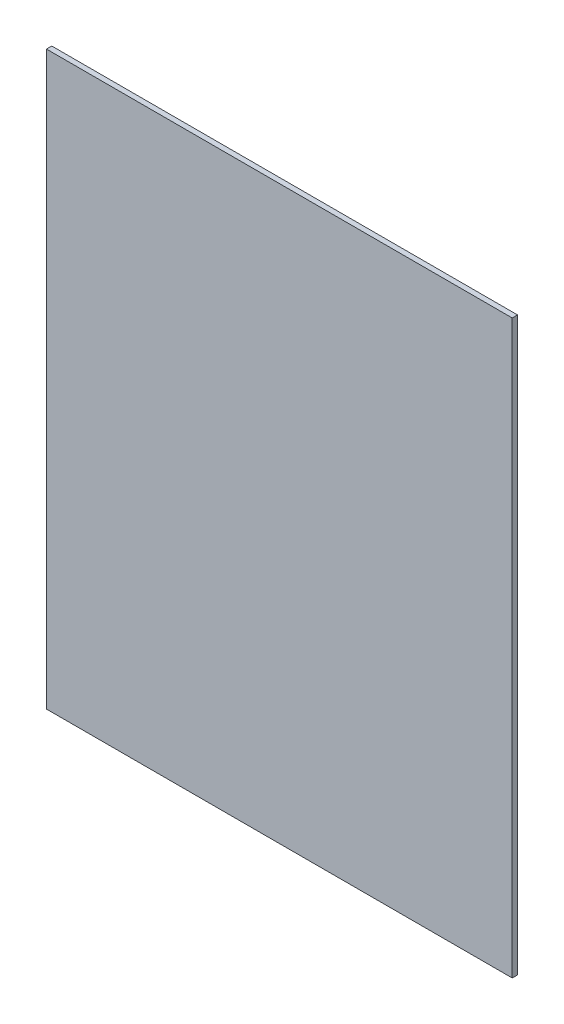
SolidWorks part; units mm, degrees
material "6061-T6 (SS)"
ref_plane "Front Plane" through (0, 0, 0) normal (0, 0, 1) x (1, 0, 0)
ref_plane "Top Plane" through (0, 0, 0) normal (0, 1, 0) x (1, 0, 0)
ref_plane "Right Plane" through (0, 0, 0) normal (1, 0, 0) x (0, 0, -1)
sketch "Sketch1" plane through (0, 0, 0) normal (0, 0, 1) x (1, 0, 0)
  line L1 (0, 0) -> (-279.4, 0)
  line L2 (0, 0) -> (0, -342.9)
  line L3 (0, -342.9) -> (-279.4, -342.9)
  line L4 (-279.4, 0) -> (-279.4, -342.9)
  dimension "D1" = 342.9
  dimension "D2" = 279.4
extrude "Boss-Extrude1" add sketch "Sketch1" along normal blind 3.175
